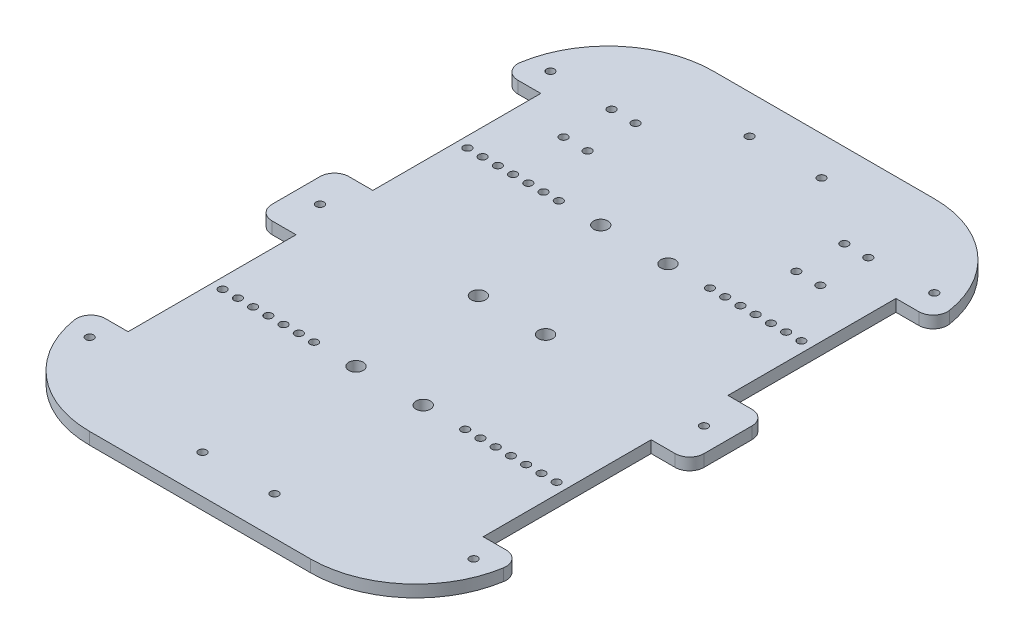
SolidWorks part; units mm, degrees
ref_plane "Ön Düzlem" through (0, 0, 0) normal (0, 0, 1) x (1, 0, 0)
ref_plane "Üst Düzlem" through (0, 0, 0) normal (0, 1, 0) x (1, 0, 0)
ref_plane "Sağ Düzlem" through (0, 0, 0) normal (1, 0, 0) x (0, 0, -1)
sketch "Sketch2" plane through (0, 0, 0) normal (0, 1, 0) x (1, 0, 0)
  line L0 (-74, -86) -> (-74, -51) construction
  line L1 (46, -130) -> (-46, -130)
  line L2 (90, -10) -> (90, 10)
  line L3 (46, 130) -> (-46, 130)
  line L4 (-90, -10) -> (-90, 10)
  line L5 (90, -130) -> (-90, 130) construction
  line L6 (90, 130) -> (-90, -130) construction
  line L7 (-83.5233, 86) -> (-74, 86)
  line L9 (-84, 16) -> (-74, 16)
  line L10 (-74, 86) -> (-74, 16)
  line L11 (-83.5233, -86) -> (-74, -86)
  line L13 (-84, -16) -> (-74, -16)
  line L14 (-74, -86) -> (-74, -16)
  line L15 (83.5233, 86) -> (74, 86)
  line L17 (84, 16) -> (74, 16)
  line L18 (74, 86) -> (74, 16)
  line L19 (83.5233, -86) -> (74, -86)
  line L21 (84, -16) -> (74, -16)
  line L22 (74, -86) -> (74, -16)
  line L23 (-74, 51) -> (74, 51) construction
  line L24 (-74, -51) -> (74, -51) construction
  arc A2 (-46, -130) -> (-89.4481, -92.9474) centre (-46, -86) cw
  arc A3 (-89.4481, 92.9474) -> (-46, 130) centre (-46, 86) cw
  arc A4 (89.4481, 92.9474) -> (46, 130) centre (46, 86) ccw
  arc A5 (89.4481, -92.9474) -> (46, -130) centre (46, -86) cw
  arc A6 (-84, 16) -> (-90, 10) centre (-84, 10) ccw
  arc A7 (-84, -16) -> (-90, -10) centre (-84, -10) cw
  arc A8 (90, 10) -> (84, 16) centre (84, 10) ccw
  arc A9 (90, -10) -> (84, -16) centre (84, -10) cw
  arc A10 (-89.4481, -92.9474) -> (-83.5233, -86) centre (-83.5233, -92) cw
  arc A11 (83.5233, -86) -> (89.4481, -92.9474) centre (83.5233, -92) cw
  arc A12 (-89.4481, 92.9474) -> (-83.5233, 86) centre (-83.5233, 92) ccw
  arc A13 (89.4481, 92.9474) -> (83.5233, 86) centre (83.5233, 92) cw
  point P0 (0, 0)
  point P34 (-90, -16)
  point P39 (90, -16)
  point P46 (-90, 86)
  point P49 (90, 86)
  dimension "D3" = 44
  dimension "D4" = 44
  dimension "D5" = 44
  dimension "D6" = 44
  dimension "D15" = 6
  dimension "D16" = 6
  dimension "D17" = 6
  dimension "D18" = 6
  dimension "D19" = 6
  dimension "D20" = 6
  dimension "D21" = 6
  dimension "D22" = 6
  dimension "D1" = 260
  dimension "D2" = 180
  dimension "D7" = 16
  dimension "D8" = 70
  dimension "D9" = 16
  dimension "D10" = 70
  dimension "D11" = 70
  dimension "D12" = 16
  dimension "D13" = 16
  dimension "D14" = 70
extrude "Boss-Extrude4" add sketch "Sketch2" along normal blind 5
sketch "Sketch5" plane through (0, 5, 0) normal (0, 1, 0) x (1, 0, 0)
  line L0 (-53.5, 75) -> (-43.5, 75) construction
  line L1 (-43.5, 75) -> (-43.5, 95) construction
  line L2 (-43.5, 95) -> (-43.5808, 94.9851) construction
  line L3 (-43.5808, 94.9851) -> (-53.5, 95) construction
  line L4 (-74, 86) -> (-74, 16) construction
  line L5 (53.5, 95) -> (43.5, 95) construction
  line L6 (43.5, 95) -> (43.5, 75) construction
  line L7 (43.5, 75) -> (53.5, 75) construction
  line L8 (74, 16) -> (74, 86) construction
  circle A0 centre (-69.6, -51) radius 1.65
  circle A1 centre (-63.25, -51) radius 1.65
  circle A2 centre (-56.9, -51) radius 1.65
  circle A3 centre (-50.55, -51) radius 1.65
  circle A4 centre (-44.2, -51) radius 1.65
  circle A5 centre (-37.85, -51) radius 1.65
  circle A6 centre (-31.5, -51) radius 1.65
  circle A7 centre (31.5, -51) radius 1.65
  circle A8 centre (37.85, -51) radius 1.65
  circle A9 centre (44.2, -51) radius 1.65
  circle A10 centre (50.55, -51) radius 1.65
  circle A11 centre (56.9, -51) radius 1.65
  circle A12 centre (63.25, -51) radius 1.65
  circle A13 centre (69.6, -51) radius 1.65
  circle A14 centre (69.6, 51) radius 1.65
  circle A15 centre (63.25, 51) radius 1.65
  circle A16 centre (56.9, 51) radius 1.65
  circle A17 centre (50.55, 51) radius 1.65
  circle A18 centre (44.2, 51) radius 1.65
  circle A19 centre (37.85, 51) radius 1.65
  circle A20 centre (31.5, 51) radius 1.65
  circle A21 centre (-31.5, 51) radius 1.65
  circle A22 centre (-37.85, 51) radius 1.65
  circle A23 centre (-44.2, 51) radius 1.65
  circle A24 centre (-50.55, 51) radius 1.65
  circle A25 centre (-56.9, 51) radius 1.65
  circle A26 centre (-63.25, 51) radius 1.65
  circle A27 centre (-69.6, 51) radius 1.65
  circle A29 centre (-14, -51) radius 3
  circle A30 centre (14, -51) radius 3
  circle A31 centre (14, 51) radius 3
  circle A32 centre (-14, 51) radius 3
  circle A33 centre (-14, 0) radius 3
  circle A34 centre (14, 0) radius 3
  circle A35 centre (-80, 96) radius 1.65
  circle A36 centre (-80, 0) radius 1.65
  circle A37 centre (80, 0) radius 1.65
  circle A38 centre (-80, -96) radius 1.65
  circle A39 centre (80, -96) radius 1.65
  circle A40 centre (80, 96) radius 1.65
  circle A41 centre (-15, -114) radius 1.65
  circle A42 centre (15, -114) radius 1.65
  circle A43 centre (15, 114) radius 1.65
  circle A44 centre (-15, 114) radius 1.65
  circle A45 centre (-53.5, 95) radius 1.65
  circle A46 centre (-53.5, 75) radius 1.65
  circle A47 centre (-43.5, 75) radius 1.65
  circle A48 centre (-43.5, 95) radius 1.65
  circle A49 centre (43.5, 75) radius 1.65
  circle A50 centre (53.5, 75) radius 1.65
  circle A51 centre (43.5, 95) radius 1.65
  circle A52 centre (53.5, 95) radius 1.65
  dimension "D1" = 20.5
  dimension "D2" = 20.5
extrude "Cut-Extrude1" cut sketch "Sketch5" against normal through all
